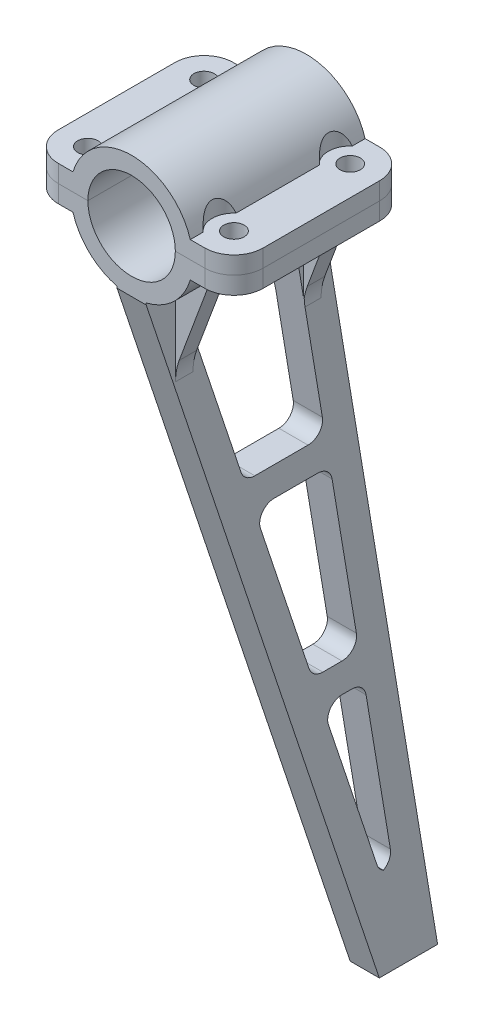
SolidWorks part; units mm, degrees
other "Leg With Lower Clamp"
other "Upper Clamp for Leg" parameters "D1"=13.8345, "D2"=14, "D5"=6.0948, "D3"=6.5463, "D4"=5.3587
ref_plane "Front Plane" through (0, 0, 0) normal (0, 0, 1) x (1, 0, 0)
ref_plane "Top Plane" through (0, 0, 0) normal (0, 1, 0) x (1, 0, 0)
ref_plane "Right Plane" through (0, 0, 0) normal (1, 0, 0) x (0, 0, -1)
sketch "Sketch1" plane through (0, 0, 0) normal (0, 0, 1) x (1, 0, 0)
  line L0 (-7.5, 0) -> (-17.5623, 0)
  line L1 (-17.5623, 0) -> (-17.5623, -3)
  line L2 (-17.5623, -3) -> (-10.0623, -3)
  line L3 (7.5, 0) -> (17.5623, 0)
  line L4 (17.5623, 0) -> (17.5623, -3)
  line L5 (17.5623, -3) -> (10.0623, -3)
  arc A0 (-7.5, 0) -> (7.5, 0) centre (0, 0) ccw
  arc A1 (-10.0623, -3) -> (10.0623, -3) centre (0, 0) ccw
  arc A3 (-10.5, 0) -> (10.5, 0) centre (0, 0) ccw construction
  dimension "D2" = 3
  dimension "D3" = 7.5
  dimension "D4" = 7.5
extrude "Lower Clamp" add sketch "Sketch1" along normal blind 30
sketch "Sketch7" plane through (0, 0, 0) normal (0, 0, 1) x (1, 0, 0)
  line L12 (-7.5, 0) -> (-17.5623, 0)
  line L15 (-17.5623, 0) -> (-17.5623, 3)
  line L16 (-17.5623, 3) -> (-10.0623, 3)
  line L17 (7.5, 0) -> (17.5623, 0)
  line L18 (17.5623, 0) -> (17.5623, 3)
  line L19 (17.5623, 3) -> (10.0623, 3)
  arc A1 (10.5, 0) -> (-10.5, 0) centre (0, 0) ccw construction
  arc A5 (7.5, 0) -> (-7.5, 0) centre (0, 0) ccw
  arc A6 (-7.5, 0) -> (7.5, 0) centre (0, 0) ccw construction
  arc A7 (10.0623, 3) -> (-10.0623, 3) centre (0, 0) ccw
  dimension "D2" = 3
  dimension "D1" = 3
extrude "Upper Clamp" add sketch "Sketch7" along normal through all separate body contours A7 L16 L15 L12 A5 L17 L18 L19
sketch "Sketch5" plane through (0, 0, 0) normal (0, 1, 0) x (1, 0, 0)
  line L0 (-17.5623, -15) -> (17.5623, -15) construction
  line L1 (-17.5623, -30) -> (-17.5623, 0) construction
  line L2 (17.5623, -30) -> (17.5623, 0) construction
  line L3 (0, 0) -> (0, -30) construction
  line L4 (-7.5, -30) -> (7.5, -30) construction
  line L5 (17.5623, 0) -> (7.5, 0) construction
  circle A0 centre (12.5312, -5.0312) radius 1.75
  circle A1 centre (12.5312, -24.9688) radius 1.75
  circle A2 centre (-12.5312, -24.9688) radius 1.75
  circle A3 centre (-12.5312, -5.0312) radius 1.75
  point P15 (12.5312, 0)
  dimension "D3" = 3.5
  dimension "D2" = 5.0312
extrude "Screw Holes" cut sketch "Sketch5" against normal through all and the other way through all
fillet "Lower Clamp Fillet" radius 5 4 edges at (17.5623, -1.5, 0) (-17.5623, -1.5, 0) (17.5623, -1.5, 30) (-17.5623, -1.5, 30)
fillet "Upper Clamp Fillet" radius 5 4 edges at (-17.5623, 1.5, 0) (-17.5623, 1.5, 30) (17.5623, 1.5, 0) (17.5623, 1.5, 30)
ref_plane "Leg Top Plane" through (0, -10.5, 0) normal (0, -1, 0) x (-1, 0, 0)
sketch "Sketch3" plane through (0, -10.5, 0) normal (0, -1, 0) x (-1, 0, 0)
  line L0 (-2.5, 0) -> (2.5, 0)
  line L2 (2.5, 0) -> (2.5, -30)
  line L4 (2.5, -30) -> (-2.5, -30)
  line L5 (-2.5, -30) -> (-2.5, 0)
  line L6 (-10.0623, -30) -> (10.0623, -30) construction
  point P3 (0, 0)
  dimension "D1" = 5
extrude "Lower Clamp Base" add sketch "Sketch3" against normal blind 3
ref_plane "Leg Base Plane" through (0, -130.5, 0) normal (0, -1, 0) x (-1, 0, 0)
sketch "Sketch4" plane through (0, -130.5, 0) normal (0, -1, 0) x (-1, 0, 0)
  line L5 (-2.5, 20) -> (2.5, 20)
  line L6 (-2.5, 20) -> (-2.5, 10)
  line L7 (-2.5, 10) -> (2.5, 10)
  line L8 (2.5, 20) -> (2.5, 10)
  point P6 (0, 10)
  dimension "D1" = 10
  dimension "D2" = 5
  dimension "D3" = 10
loft "Leg" add profiles "Sketch4" section "Sketch4" section face at (0, -10.5, 15) connector at (-2.5, -130.5, -20) connector at (-2.5, -10.5, 0)
sketch "Sketch8" plane through (2.5, 0, 0) normal (1, 0, 0) x (0, 0, -1)
  line L10 (-23.1635, -15.198) -> (-4.286, -15.198)
  line L11 (-4.286, -15.198) -> (0.714, -45.198)
  line L12 (0.714, -45.198) -> (-13.1635, -45.198)
  line L13 (-13.1635, -45.198) -> (-23.1635, -15.198)
  line L14 (-11.4969, -50.198) -> (1.5474, -50.198)
  line L15 (1.5474, -50.198) -> (6.5474, -80.198)
  line L16 (6.5474, -80.198) -> (-1.4969, -80.198)
  line L17 (-1.4969, -80.198) -> (-11.4969, -50.198)
  line L18 (0.1698, -85.198) -> (7.3807, -85.198)
  line L19 (7.3807, -85.198) -> (12.3807, -115.198)
  line L20 (12.3807, -115.198) -> (10.1698, -115.198)
  line L21 (10.1698, -115.198) -> (0.1698, -85.198)
  line L22 (20, -130.5) -> (0, -10.5) construction
  line L23 (10, -130.5) -> (-30, -10.5) construction
  line L24 (-30, -10.198) -> (0, -10.198) construction
  dimension "D1" = 5
  dimension "D2" = 5
  dimension "D3" = 5
  dimension "D4" = 5
  dimension "D5" = 5
  dimension "D6" = 30
  dimension "D7" = 30
  dimension "D8" = 30
extrude "Lightening Holes" cut sketch "Sketch8" against normal through all
fillet "Removing Stress Concentrations" radius 2.5 12 edges at (0, -85.198, -0.1698) (0, -50.198, 11.4969) (0, -15.198, 23.1635) (0, -115.198, -10.1698) (0, -80.198, 1.4969) (0, -45.198, 13.1635) (0, -45.198, -0.714) (0, -80.198, -6.5474) (0, -115.198, -12.3807) (0, -85.198, -7.3807) (0, -50.198, -1.5474) (0, -15.198, 4.286)
sketch "Sketch9" plane through (0, 3, 0) normal (0, 1, 0) x (1, 0, 0)
  line L0 (0, 0) -> (0, -30) construction
  line L1 (-10.0623, -30) -> (10.0623, -30) construction
  line L2 (-17.5623, -15) -> (17.5623, -15) construction
  line L3 (-17.5623, -25) -> (-17.5623, -5) construction
  line L4 (17.5623, -25) -> (17.5623, -5) construction
  circle A0 centre (12.5312, -5.0312) radius 1.75 construction
  circle A1 centre (12.5312, -5.0312) radius 1.75 construction
  circle A2 centre (12.5312, -5.0312) radius 3.75
  circle A3 centre (12.5312, -24.9688) radius 3.75
  circle A4 centre (-12.5312, -24.9688) radius 3.75
  circle A5 centre (-12.5312, -5.0312) radius 3.75
  dimension "D1" = 2
extrude "Upper Clamp Screw Clearance" cut sketch "Sketch9" along normal through all
sketch "Sketch10" plane through (0, -3, 0) normal (0, -1, 0) x (1, 0, 0)
  line L0 (-17.5623, 15) -> (17.5623, 15) construction
  line L1 (-17.5623, 25) -> (-17.5623, 5) construction
  line L2 (17.5623, 25) -> (17.5623, 5) construction
  line L3 (0, 30) -> (0, 0) construction
  line L4 (2.5, 30) -> (-2.5, 30) construction
  circle A0 centre (12.5312, 24.9688) radius 1.75 construction
  circle A1 centre (12.5312, 24.9688) radius 1.75 construction
  circle A2 centre (12.5312, 24.9688) radius 3.75
  circle A3 centre (12.5312, 5.0312) radius 3.75
  circle A4 centre (-12.5312, 5.0312) radius 3.75
  circle A5 centre (-12.5312, 24.9688) radius 3.75
  dimension "D1" = 2
extrude "Lower Clamp Screw Clearance" cut sketch "Sketch10" along normal through all
ref_plane "Plane1" through (0, 0, 24.977) normal (0, 0, 1) x (1, 0, 0)
sketch "Sketch11" plane through (0, 0, 24.977) normal (0, 0, 1) x (1, 0, 0)
  line L0 (0, -7.5) -> (0, -28.0317) construction
  line L1 (-8.7812, -5.7568) -> (-2.5, -22.6261)
  line L2 (2.5, -25.5691) -> (2.5, -10.198)
  line L3 (2.5, -22.6261) -> (2.5, -10.198)
  line L4 (8.7812, -5.7568) -> (2.5, -22.6261)
  line L5 (-2.5, -22.6261) -> (-2.5, -10.198)
  line L6 (2.5, -130.5) -> (2.5, -10.5) construction
  arc A0 (2.5, -10.198) -> (8.7812, -5.7568) centre (0, 0) ccw
  arc A1 (2.5, -10.198) -> (8.7812, -5.7568) centre (0, 0) ccw
  arc A2 (-7.5, 0) -> (7.5, 0) centre (0, 0) ccw construction
  arc A3 (-2.5, -10.198) -> (-8.7812, -5.7568) centre (0, 0) cw
  point P14 (2.5, -22.6261)
extrude "Boss-Extrude1" add sketch "Sketch11" against normal blind 3
sketch "Sketch12" plane through (0, 0, 0) normal (0, 0, -1) x (-1, 0, 0)
  line L2 (-8.7812, -5.7568) -> (-2.5, -22.6261)
  line L3 (-2.5, -22.6261) -> (-2.5, -18.7577)
  line L4 (-8.7812, -5.7568) -> (-2.5, -22.6261)
  line L5 (-2.5, -22.6261) -> (-2.5, -18.7577)
  line L6 (2.5, -10.198) -> (2.5, -16.677)
  line L7 (2.5, -22.6261) -> (8.7812, -5.7568)
  line L8 (2.5, -10.198) -> (2.5, -16.677)
  line L9 (2.5, -22.6261) -> (8.7812, -5.7568)
  line L12 (-2.5, -18.7577) -> (-2.5, -16.677)
  line L13 (-2.5, -18.7577) -> (-2.5, -16.677)
  line L14 (-2.5, -16.677) -> (-2.5, -10.198)
  line L15 (-2.5, -16.677) -> (-2.5, -10.198)
  line L16 (2.5, -16.677) -> (2.5, -18.7577)
  line L17 (2.5, -16.677) -> (2.5, -18.7577)
  line L18 (2.5, -18.7577) -> (2.5, -22.6261)
  line L19 (2.5, -18.7577) -> (2.5, -22.6261)
  arc A1 (-8.7812, -5.7568) -> (-2.5, -10.198) centre (0, 0) ccw
  arc A2 (-8.7812, -5.7568) -> (-2.5, -10.198) centre (0, 0) ccw
  arc A3 (2.5, -10.198) -> (8.7812, -5.7568) centre (0, 0) ccw
  arc A4 (2.5, -10.198) -> (8.7812, -5.7568) centre (0, 0) ccw
  dimension "D1" = 0
  dimension "D2" = 0
extrude "Boss-Extrude2" add sketch "Sketch12" against normal blind 3
fillet "Fillet1" radius 10 8 edges at (-2.5, -22.6261, 1.5) (-8.7812, -5.7568, 1.5) (-2.5, -22.6261, 23.477) (2.5, -22.6261, 23.477) (2.5, -22.6261, 1.5) (8.7812, -5.7568, 1.5)
equation "\"D4@Sketch1\"=\"D3@Sketch1\""
equation "\"D2@Sketch5\"=\"D1@Sketch5\""
